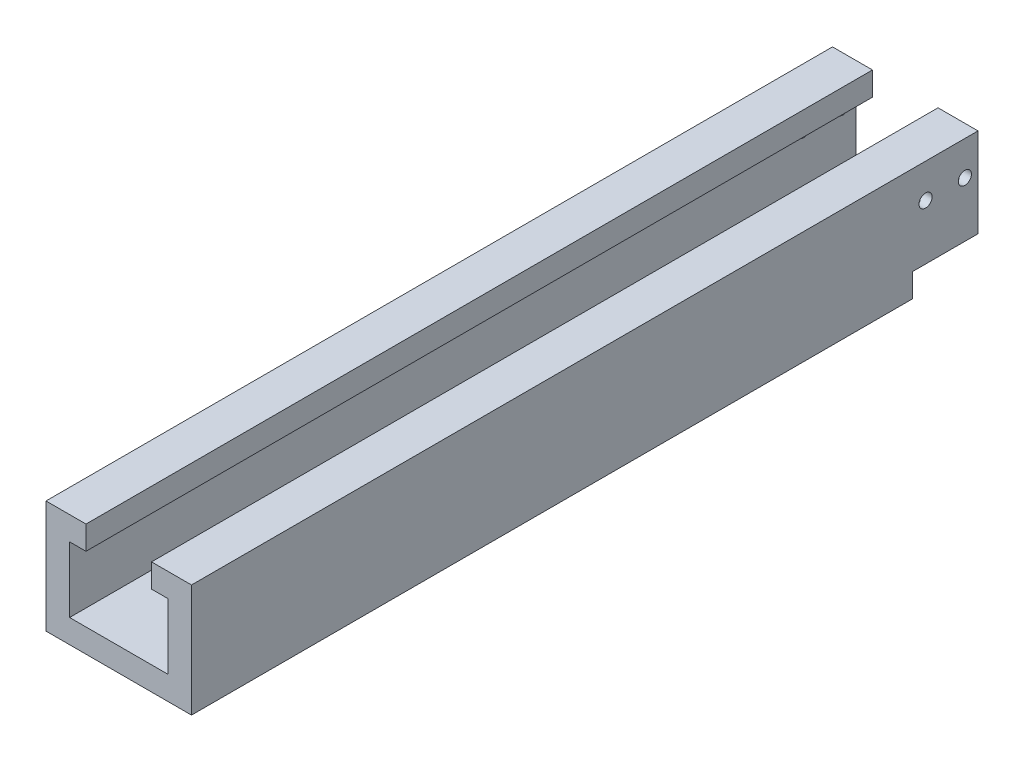
SolidWorks part; units mm, degrees
material "Beech"
ref_plane "Front Plane" through (0, 0, 0) normal (0, 0, 1) x (1, 0, 0)
ref_plane "Top Plane" through (0, 0, 0) normal (0, 1, 0) x (1, 0, 0)
ref_plane "Right Plane" through (0, 0, 0) normal (1, 0, 0) x (0, 0, -1)
sketch "Sketch1" plane through (0, 0, 0) normal (0, 0, 1) x (1, 0, 0)
  line L1 (0, 0) -> (111, 0)
  line L2 (0, 0) -> (0, 18)
  line L3 (0, 18) -> (111, 18)
  line L4 (111, 0) -> (111, 18)
  dimension "D1" = 18
  dimension "D2" = 111
extrude "baseplate" add sketch "Sketch1" along normal blind 600
sketch "Sketch2" plane through (0, 18, 0) normal (0, 1, 0) x (1, 0, 0)
  line L0 (111, -600) -> (0, -600) construction
  line L1 (0, 0) -> (18, 0)
  line L2 (0, 0) -> (0, -600)
  line L3 (0, -600) -> (18, -600)
  line L4 (18, 0) -> (18, -600)
  dimension "D1" = 18
extrude "side_rail" add sketch "Sketch2" along normal blind 50
sketch "Sketch3" plane through (0, 68, 0) normal (0, 1, 0) x (1, 0, 0)
  line L0 (111, -600) -> (18, -600) construction
  line L1 (0, 0) -> (30.5, 0)
  line L2 (0, 0) -> (0, -600)
  line L3 (0, -600) -> (30.5, -600)
  line L4 (30.5, 0) -> (30.5, -600)
  dimension "D1" = 30.5
extrude "keeper rail" add sketch "Sketch3" along normal blind 18
ref_plane "longitudinal midplane" through (55.5, 0, 0) normal (-1, 0, 0) x (0, 0, 1)
mirror "mirror rails" about plane through (55.5, 0, 0) normal (-1, 0, 0) of "keeper rail", "side_rail"
sketch "Sketch5" plane through (0, 0, 0) normal (0, -1, 0) x (1, 0, 0)
  line L0 (111, 600) -> (111, 0) construction
  line L1 (0, 0) -> (111, 0)
  line L2 (0, 0) -> (0, 50)
  line L3 (0, 50) -> (111, 50)
  line L4 (111, 0) -> (111, 50)
  dimension "D1" = 50
extrude "lap joint cutout" cut sketch "Sketch5" against normal blind 18
hole_wizard "lap joint bolt hole pattern" positions "Sketch7" profile "Sketch9" hole size "M6" standard "ANSI Metric"
sketch "Sketch7" plane through (0, 18, 0) normal (0, -1, 0) x (-1, 0, 0)
  line L1 (-102, -10) -> (-9, -10)
  line L2 (-102, -10) -> (-102, -40)
  line L3 (-102, -40) -> (-9, -40)
  line L4 (-9, -10) -> (-9, -40)
  line L5 (-102, 0) -> (-102, -10)
  line L6 (-93, 0) -> (-111, 0) construction
  line L8 (-9, -10) -> (-9, 0)
  line L9 (0, 0) -> (-18, 0) construction
  line L10 (-9, -25) -> (0, -25)
  line L11 (0, -50) -> (0, 0) construction
  point P1 (-102, -10)
  point P2 (-9, -40)
  point P113 (-102, -40)
  point P114 (-9, -10)
sketch "Sketch9" plane through (102, 18, 10) normal (1, 0, 0) x (0, 0, -1)
  line L0 (0, 0) -> (0, 58.9828)
  line L1 (0, 58.9828) -> (3.3, 57)
  line L2 (3.3, 57) -> (3.3, 0)
  line L5 (3.3, 0) -> (0, 0)
  line L10 (0, 58.9828) -> (-3.3, 57) construction
  line L11 (0, -6.35) -> (0, 107.95) construction
  dimension "Hole Dia." = 6.6
  dimension "Hole Depth" = 57
  dimension "Drill Angle" = 118
hole_wizard "fixed bearing block bolt clearance holes" positions "Sketch10" profile "Sketch11" hole size "M6" standard "ANSI Metric" end condition through all
sketch "Sketch10" plane through (0, 18, 0) normal (0, 1, 0) x (1, 0, 0)
  line L0 (37.5, -535) -> (73.5, -535)
  line L2 (55.5, -535) -> (55.5, -600)
  line L3 (93, -600) -> (18, -600) construction
  point P0 (37.5, -535)
  point P2 (73.5, -535)
  dimension "D1" = 36
  dimension "D2" = 65
sketch "Sketch11" plane through (37.5, 18, 535) normal (1, 0, 0) x (0, 0, 1)
  line L0 (0, 0) -> (0, 18)
  line L1 (0, 18) -> (3.3, 18)
  line L2 (3.3, 18) -> (3.3, 0)
  line L5 (3.3, 0) -> (0, 0)
  line L11 (0, -6.35) -> (0, 107.95) construction
  dimension "Thru Hole Dia." = 6.6
  dimension "Thru Hole Depth" = 18
ref_axis "bottom foot bolt hole axis" through (102, 81.8786, 10) along (0, -1, 0)
ref_axis "top foot bolt hole axis" through (102, 75, 40) along (0, -1, 0)
hole_wizard "cross dowel bolt clearance holes" positions "Sketch14" profile "Sketch15" hole size "Ø10.0" standard "ANSI Metric" end condition through all
sketch "Sketch14" plane through (111, 0, 0) normal (1, 0, 0) x (0, 0, -1)
  line L0 (-40, 75) -> (-40, 18) construction
  line L1 (-10, 81.8786) -> (-10, 18) construction
  line L2 (-40, 60) -> (-10, 60)
  line L4 (-36.7, 75) -> (-43.3, 75) construction
  line L5 (-6.7, 75) -> (-13.3, 75) construction
  line L6 (-36.7, 75) -> (-43.3, 75)
  line L7 (-6.7, 75) -> (-13.3, 75)
  point P0 (-40, 60)
  point P4 (-10, 60)
  dimension "D1" = 15
sketch "Sketch15" plane through (111, 60, 40) normal (0, 1, 0) x (0, 0, -1)
  line L0 (0, 0) -> (0, 111)
  line L1 (0, 111) -> (5, 111)
  line L2 (5, 111) -> (5, 0)
  line L5 (5, 0) -> (0, 0)
  line L11 (0, -6.35) -> (0, 107.95) construction
  dimension "Thru Hole Dia." = 10
  dimension "Thru Hole Depth" = 111
equation "\"board_thickness\" = 18mm"
equation "\"way_width\"= 75mm"
equation "\"way_thickness\"= 50mm"
equation "\"radial_clearance\"= 0.1mm"
equation "\"slider_width\"= \"way_width\"-2* \"radial_clearance\" - 2*0.65"
equation "\"slider_thickness\" = \"way_thickness\" - 2 * \"radial_clearance\""
equation "\"column_width\"= \"way_width\" + 2 * \"board_thickness\""
equation "\"D1@Sketch1\"=\"board_thickness\""
equation "\"D2@Sketch1\"=\"column_width\""
equation "\"D1@Sketch2\"=\"board_thickness\""
equation "\"D1@keeper rail\"=\"board_thickness\""
equation "\"boxway_slot_width\" = 50mm"
equation "\"keeper_rail_width\" = (\"column_width\" - \"boxway_slot_width\")/2"
equation "\"D1@Sketch3\"=\"keeper_rail_width\""
equation "\"slider_length\" = 125mm"
equation "\"nut_diameter\"= 22mm"
equation "\"nut_length\"= 15mm"
equation "\"leadscrew_diameter\"= 10mm"
equation "\"leadscrew_radial_clearance\"= 1mm"
equation "\"bearing_bolt_pattern_width\" = 30mm"
equation "\"bearing_bolt_pattern_height\" = 75mm"
equation "\"desktop_bolt_pattern_width\" = 30mm"
equation "\"desktop_bolt_pattern_height\" = 30mm"
equation "\"bearing_bolt_nut_counterbore_diameter\" = 12mm"
equation "\"bearing_bolt_nut_counterbore_depth\"= 10mm"
equation "\"desktop_depth\"= 500mm"
equation "\"desktop_width\"= 650mm"
equation "\"desktop_thickness\"= 18mm"
equation "\"leg_height\"=100mm"
equation "\"leg_width\"=18mm"
equation "\"leg_length\"=500mm"
equation "\"D1@lap joint cutout\" = \"leg_width\""
equation "\"lap_joint_height\" = 50mm"
equation "\"lap_dowel_diameter\"= 8mm"
equation "\"lap_dowel_hole_z_spacing\"=30"
equation "\"D1@Sketch5\"=\"lap_joint_height\""
equation "\"D1@Sketch7\"=\"lap_dowel_hole_z_spacing\""
